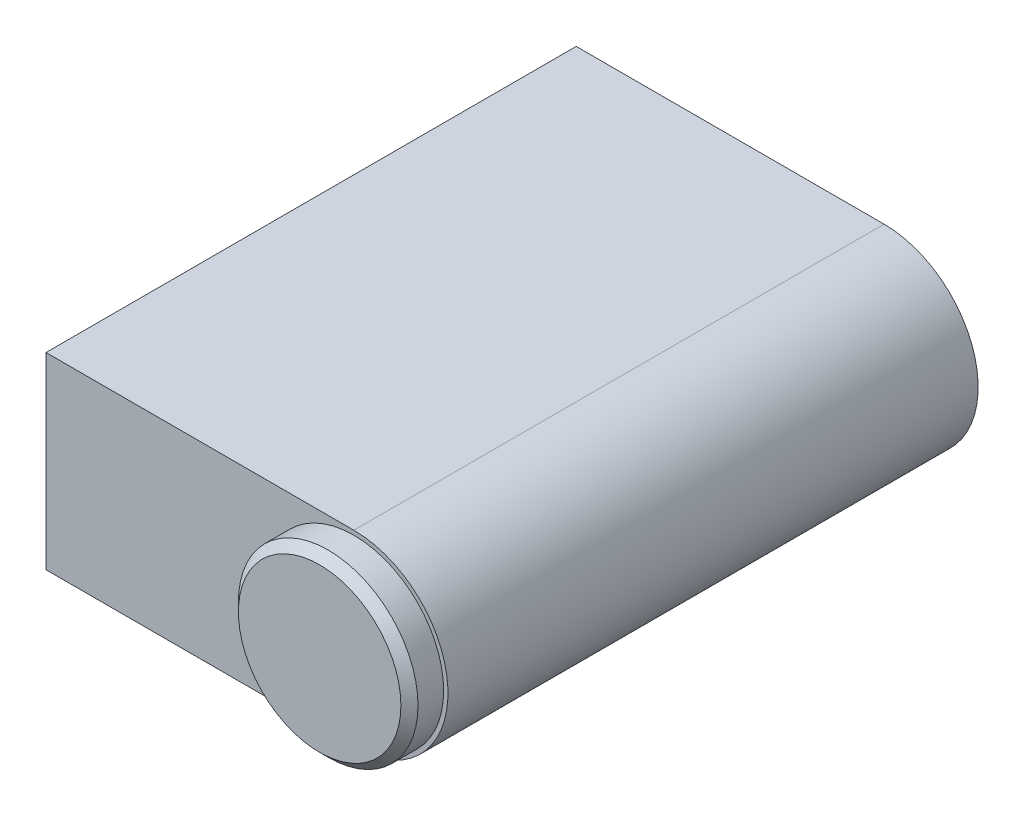
SolidWorks part; units mm, degrees
ref_plane "Plan de face" through (0, 0, 0) normal (0, 0, 1) x (1, 0, 0)
ref_plane "Plan de dessus" through (0, 0, 0) normal (0, 1, 0) x (1, 0, 0)
ref_plane "Plan de droite" through (0, 0, 0) normal (1, 0, 0) x (0, 0, -1)
sketch "Esquisse1" plane through (0, 0, 0) normal (0, 0, 1) x (1, 0, 0)
  line L0 (0, 5.5) -> (-18, 5.5)
  line L1 (-18, 5.5) -> (-18, -5.5)
  line L2 (-18, -5.5) -> (0, -5.5)
  arc A0 (0, -5.5) -> (0, 5.5) centre (0, 0) ccw
  dimension "D1" = 18
  dimension "D2" = 5.5
extrude "Boss.-Extru.1" add sketch "Esquisse1" along normal blind 31
sketch "Esquisse2" plane through (-18, 0, 0) normal (-1, 0, 0) x (0, 0, 1)
  line L0 (31, 5.5) -> (0, 5.5) construction
  line L1 (30, -4.5) -> (3, -4.5)
  line L2 (30, -4.5) -> (30, 4.5)
  line L3 (30, 4.5) -> (3, 4.5)
  line L4 (3, -4.5) -> (3, 4.5)
  line L5 (30, -4.5) -> (3, 4.5) construction
  line L6 (30, 4.5) -> (3, -4.5) construction
  line L7 (30, 4.5) -> (31, 4.5) construction
  line L8 (31, 5.5) -> (31, -5.5) construction
  line L9 (30, 4.5) -> (30, 5.5) construction
  point P0 (16.5, 0)
  point P5 (0, 0)
  point P6 (0, 0)
  dimension "D1" = 9
  dimension "D2" = 27
  dimension "D3" = 1
extrude "Enlèv. mat.-Extru.1" cut sketch "Esquisse2" against normal blind 9
sketch "Esquisse3" plane through (0, 0, 31) normal (0, 0, 1) x (1, 0, 0)
  circle A0 centre (0, 0) radius 5.25
  dimension "D1" = 10.5
sketch "Esquisse4" plane through (0, 0, 0) normal (0, 0, -1) x (-1, 0, 0)
  line L0 (0.3096, 3.7372) -> (16.5482, 2.3918)
  line L1 (0.3096, -3.7372) -> (16.5482, -2.3918)
  arc A1 (0.3096, 3.7372) -> (0.3096, -3.7372) centre (0, 0) ccw
  arc A2 (16.5482, -2.3918) -> (16.5482, 2.3918) centre (16.35, 0) ccw
  point P1 (18.75, 0)
  point P12 (-3.75, 0)
  dimension "D1" = 7.5
  dimension "D3" = 2.4
  dimension "D4" = 22.5
chamfer "Chanfrein2" distance 0.5 angle 45 4 edges at (-18, 0, 3) (-18, -4.5, 16.5) (-18, 4.5, 16.5) (-18, 0, 30)
extrude "Enlèv. mat.-Extru.3" cut sketch "Esquisse4" against normal blind 3
sketch "Esquisse5" plane through (0, 0, 3) normal (0, 0, -1) x (-1, 0, 0)
  circle A0 centre (6, 0) radius 1.675
  point P2 (0, 0)
  dimension "D1" = 3.35
  dimension "D2" = 6
extrude "Enlèv. mat.-Extru.4" cut sketch "Esquisse5" against normal blind 4.3
sketch "Esquisse6" plane through (0, 0, 7.3) normal (0, 0, -1) x (-1, 0, 0)
  circle A0 centre (6, 0) radius 1.25
  dimension "D1" = 2.5
extrude "Enlèv. mat.-Extru.5" cut sketch "Esquisse6" against normal blind 5
chamfer "Chanfrein3" distance 0.3 angle 45 7 edges at (-4.6548, -3.3772, 3) (-4.6548, 3.3772, 3) (-8.4289, -3.0645, 0) (3.75, 0, 0) (-8.4289, 3.0645, 0) (3.75, 0, 3) (-17.3294, 2.1911, 0)
extrude "Boss.-Extru.2" add sketch "Esquisse3" along normal blind 2
chamfer "Chanfrein4" distance 0.5 angle 45 1 edges at (5.25, 0, 33)
